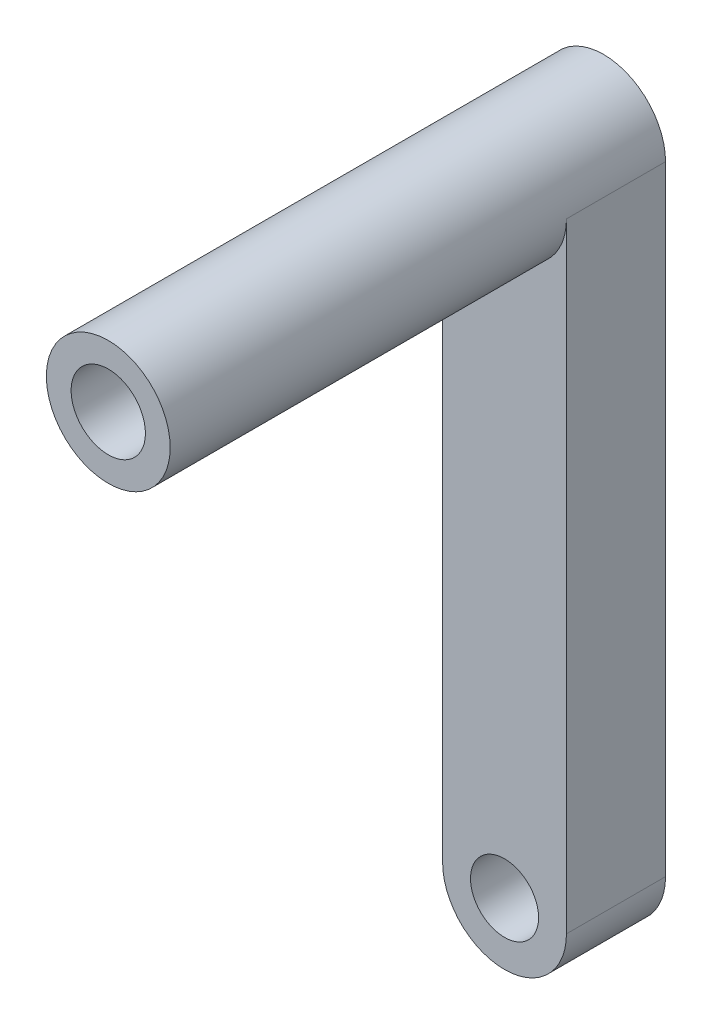
SolidWorks part; units mm, degrees
ref_plane "Front Plane" through (0, 0, 0) normal (0, 0, 1) x (1, 0, 0)
ref_plane "Top Plane" through (0, 0, 0) normal (0, 1, 0) x (1, 0, 0)
ref_plane "Right Plane" through (0, 0, 0) normal (1, 0, 0) x (0, 0, -1)
sketch "Sketch1" plane through (0, 0, 0) normal (0, 0, 1) x (1, 0, 0)
  line L0 (0, -10.1471) -> (0, 14.8529) construction
  line L1 (-2.5, -10.1471) -> (-2.5, 14.8529)
  line L2 (2.5, -10.1471) -> (2.5, 14.8529)
  arc A0 (-2.5, -10.1471) -> (2.5, -10.1471) centre (0, -10.1471) ccw
  arc A1 (2.5, 14.8529) -> (-2.5, 14.8529) centre (0, 14.8529) ccw
  circle A2 centre (0, 14.8529) radius 1.5
  circle A3 centre (0, -10.1471) radius 1.375
  arc A4 (-2.5, 14.8529) -> (2.5, 14.8529) centre (0, 14.8529) ccw
  point P3 (0, 2.3529)
  dimension "D3" = 3
  dimension "D4" = 2.75
  dimension "D6" = 3
  dimension "D1" = 25
  dimension "D2" = 25
  dimension "D5" = 5
extrude "Boss-Extrude3" add sketch "Sketch1" along normal blind 4 contours A3 A4 L1 A0 L2 region at (0, 0.9151, 0)
extrude "Boss-Extrude4" add sketch "Sketch1<6>" along normal blind 20 contours A1 A4 A2 region at (0, 17.2822, 0)
sketch "Sketch1<6>" plane through (0, 0, 0) normal (0, 0, 1) x (1, 0, 0) same geometry as "Sketch1"
